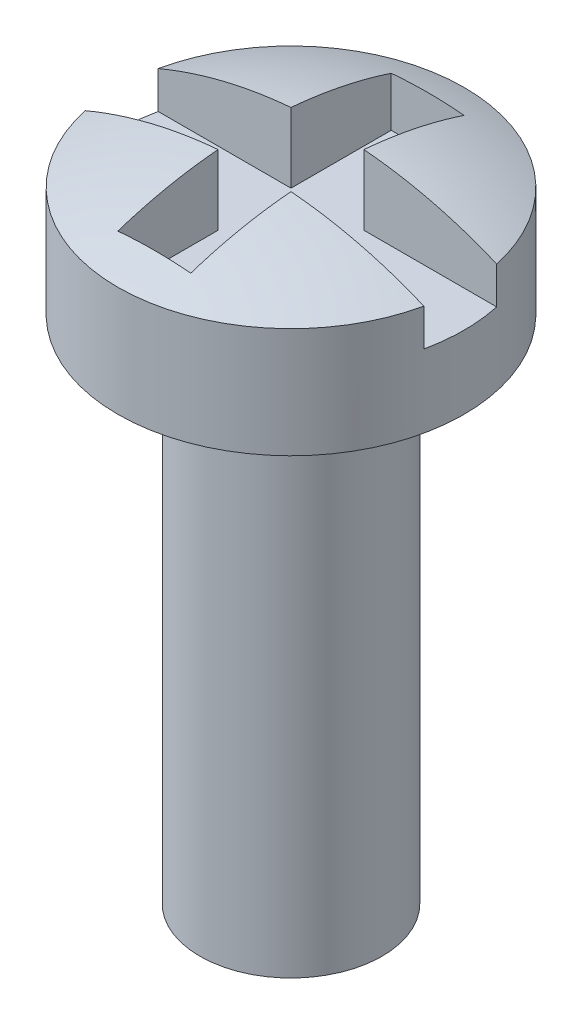
SolidWorks part; units mm, degrees
ref_plane "前视基准面" through (0, 0, 0) normal (0, 0, 1) x (1, 0, 0)
ref_plane "上视基准面" through (0, 0, 0) normal (0, 1, 0) x (1, 0, 0)
ref_plane "右视基准面" through (0, 0, 0) normal (1, 0, 0) x (0, 0, -1)
sketch "草图1" plane through (0, 0, 0) normal (0, 1, 0) x (1, 0, 0)
  circle A0 centre (0, 0) radius 1.25
  dimension "D1" = 2.5
extrude "拉伸1" add sketch "草图1" along normal blind 7
sketch "草图2" plane through (0, 7, 0) normal (0, 1, 0) x (-1, 0, 0)
  circle A0 centre (0, 0) radius 2.375
  dimension "D1" = 4.75
extrude "拉伸2" add sketch "草图2" along normal blind 2
sketch "草图3" plane through (0, 9, 0) normal (0, 1, 0) x (-1, 0, 0)
  line L0 (4.0624, 0) -> (-4.2778, 0) construction
  line L1 (0, -3.5166) -> (0, 3.738) construction
  line L3 (3.5023, -0.5) -> (-3.5023, -0.5)
  line L4 (3.5023, -0.5) -> (3.5023, 0.5)
  line L5 (3.5023, 0.5) -> (-3.5023, 0.5)
  line L6 (-3.5023, -0.5) -> (-3.5023, 0.5)
  dimension "D1" = 1
extrude "切除-拉伸1" cut sketch "草图3" against normal blind 1
sketch "草图4" plane through (0, 9, 0) normal (0, 1, 0) x (-1, 0, 0)
  line L0 (0, -3.8639) -> (0, 3.6765) construction
  line L1 (1.7727, 0) -> (-1.7019, 0) construction
  line L2 (0.5, -1.875) -> (-0.5, -1.875)
  line L3 (0.5, -1.875) -> (0.5, 1.875)
  line L4 (0.5, 1.875) -> (-0.5, 1.875)
  line L5 (-0.5, -1.875) -> (-0.5, 1.875)
  dimension "D1" = 1
  dimension "D2" = 3.75
extrude "切除-拉伸2" cut sketch "草图4" against normal blind 1
sketch "草图5" plane through (0, 0, 0) normal (1, 0, 0) x (0, 0, -1)
  line L0 (0, -2.1059) -> (0, 12.2815) construction
  line L1 (-0.5, 9) -> (-2.375, 9) construction
  line L2 (0, 10.9998) -> (-4.5494, 10.9998)
  line L3 (-4.5494, 6.9119) -> (-4.5494, 10.9998)
  line L5 (0, 10.9998) -> (0, 9)
  arc A2 (0, 9) -> (-4.5494, 6.9119) centre (0, 3) ccw
  dimension "D1" = 6
revolve "切除-旋转16" cut sketch "草图5" angle 360 about L0
